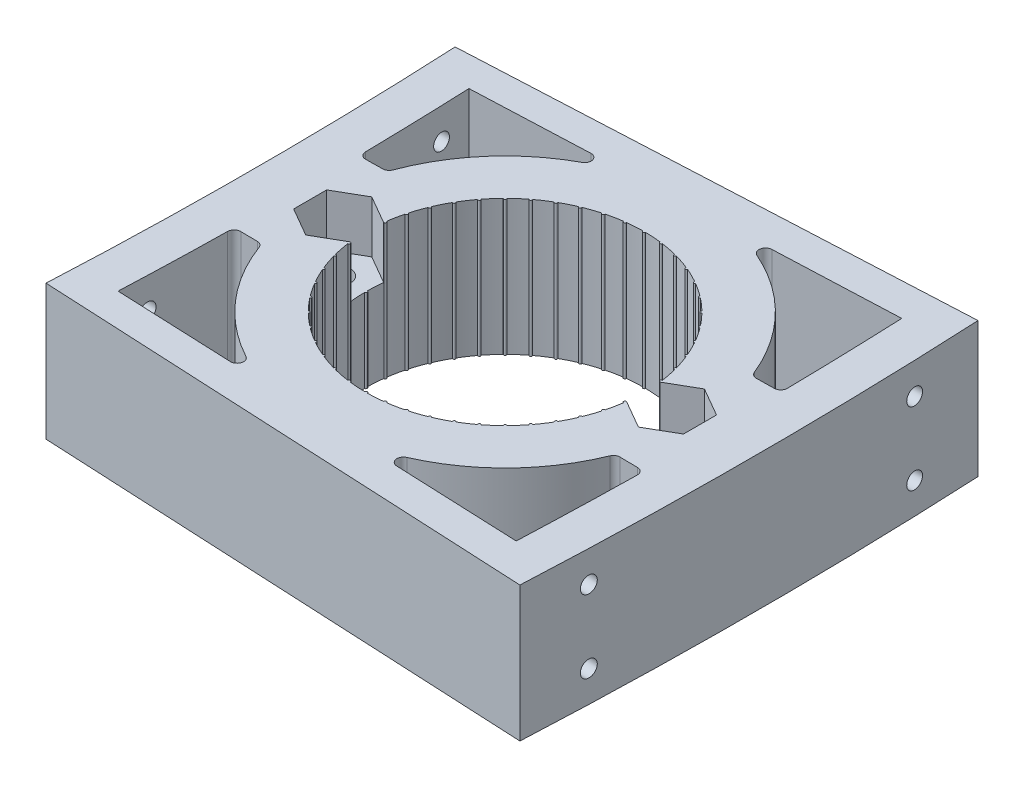
SolidWorks part; units mm, degrees
ref_plane "Front Plane" through (0, 0, 0) normal (0, 0, 1) x (1, 0, 0)
ref_plane "Top Plane" through (0, 0, 0) normal (0, 1, 0) x (1, 0, 0)
ref_plane "Right Plane" through (0, 0, 0) normal (1, 0, 0) x (0, 0, -1)
sketch "Sketch1" plane through (0, 0, 0) normal (0, 1, 0) x (1, 0, 0)
  line L0 (711.9611, 34.9764) -> (0, 0) construction
  line L1 (0, 0) -> (711.9611, -34.9764) construction
  line L2 (635.8529, 31.2375) -> (711.9611, 34.9764)
  line L3 (635.8529, -31.2375) -> (711.9611, -34.9764)
  circle A0 centre (0, 0) radius 636.6198 construction
  circle A1 centre (0, 0) radius 712.8198 construction
  arc A2 (711.9611, -34.9764) -> (711.9611, 34.9764) centre (0, 0) ccw
  arc A3 (635.8529, -31.2375) -> (635.8529, 31.2375) centre (0, 0) ccw
  dimension "D1" = 1273.2395
  dimension "D2" = 76.2
  dimension "D3" = 5.625
extrude "TrackTop" add sketch "Sketch1" along normal blind 20.6375
sketch "Sketch6" plane through (0, 0, 0) normal (0, 1, 0) x (1, 0, 0)
  line L0 (636.6198, 0) -> (0, 0) construction
  line L1 (636.6198, 0) -> (649.3198, 0) construction
  line L2 (649.3198, 0) -> (700.1198, 0) construction
  line L3 (700.1198, 0) -> (712.8198, 0) construction
  circle A0 centre (649.3198, 0) radius 1.8288
  circle A1 centre (700.1198, 0) radius 1.8288
  circle A4 centre (0, 0) radius 712.8198 construction
  circle A5 centre (0, 0) radius 636.6198 construction
  dimension "D1" = 3.6576
  dimension "D2" = 12.7
extrude "MountingHoles" cut sketch "Sketch6" along normal through all both and the other way through all
sketch "Sketch9" plane through (0, 0, 0) normal (0, 1, 0) x (1, 0, 0)
  line L0 (0, 0) -> (755.0104, 26.3655) construction
  line L1 (0, 0) -> (983.0347, 0) construction
  dimension "D1" = 2
sketch "Sketch7" plane through (0, 20.6375, 0) normal (0, 1, 0) x (1, 0, 0)
  line L0 (712.8198, 0) -> (636.6198, 0) construction
  arc A0 (711.9611, -34.9764) -> (711.9611, 34.9764) centre (0, 0) ccw construction
  arc A1 (635.8529, -31.2375) -> (635.8529, 31.2375) centre (0, 0) ccw construction
  circle A2 centre (674.7198, 0) radius 21.25
  dimension "D1" = 42.5
extrude "Cut-Extrude1" cut sketch "Sketch7" against normal through all
sketch "Sketch15" plane through (0, 0, 0) normal (0, 1, 0) x (1, 0, 0)
  line L0 (674.7198, 21.25) -> (674.7198, -21.25) construction
  circle A0 centre (674.7198, 0) radius 21.25 construction
  circle A1 centre (674.7198, 0) radius 21.25 construction
  circle A2 centre (674.7198, 21.25) radius 0.2
  point P2 (674.7198, 0)
  dimension "D1" = 0.4
sketch "Sketch16" plane through (0, 0, 0) normal (0, 0, 1) x (1, 0, 0)
  line L0 (674.7198, 0) -> (674.7198, 28.4843) construction
extrude "Boss-Extrude1" add sketch "Sketch15" along normal up to surface (20.6375 mm away) up to face at (674.7198, 20.6375, 21.25)
pattern_circular "CirPattern1" count 48 over 360 about axis through (674.7198, 0, 0) along (0, 1, 0) of "Boss-Extrude1" reverse direction yes
sketch "Sketch8" plane through (0, 20.6375, 0) normal (0, 1, 0) x (1, 0, 0)
  line L1 (653.6854, -2.5205) -> (653.6854, 2.5205)
  line L2 (653.6854, 2.5205) -> (649.3198, 5.041)
  line L3 (649.3198, 5.041) -> (644.9541, 2.5205)
  line L4 (644.9541, 2.5205) -> (644.9541, -2.5205)
  line L5 (644.9541, -2.5205) -> (649.3198, -5.041)
  line L6 (649.3198, -5.041) -> (653.6854, -2.5205)
  line L7 (704.4854, -2.5205) -> (704.4854, 2.5205)
  line L8 (704.4854, 2.5205) -> (700.1198, 5.041)
  line L9 (700.1198, 5.041) -> (695.7541, 2.5205)
  line L10 (695.7541, 2.5205) -> (695.7541, -2.5205)
  line L11 (695.7541, -2.5205) -> (700.1198, -5.041)
  line L12 (700.1198, -5.041) -> (704.4854, -2.5205)
  circle A0 centre (649.3198, 0) radius 4.3656 construction
  circle A1 centre (700.1198, 0) radius 4.3656 construction
  point P10 (644.9541, 0)
  dimension "D1" = 8.7312
extrude "Cut-Extrude2" cut sketch "Sketch8" against normal blind 7.9375
sketch "Sketch13" plane through (0, 20.6375, 0) normal (0, 1, 0) x (1, 0, 0)
  line L0 (642.4114, 26.7914) -> (705.8562, 29.4373) construction
  line L1 (642.4114, -26.7914) -> (705.8562, -29.4373) construction
  line L2 (642.4114, -26.7914) -> (0, 0) construction
  line L3 (642.4114, 26.7914) -> (0, 0) construction
  line L4 (-200000, 0) -> (200983.0347, 0) construction
  line L5 (635.8529, 31.2375) -> (711.9611, 34.9764) construction
  line L6 (642.8992, 9.525) -> (642.8992, -9.525) construction
  line L7 (706.3922, 10.4657) -> (701.9914, 10.4005)
  line L8 (642.8992, 9.525) -> (647.152, 9.588)
  line L9 (647.152, -9.588) -> (642.8992, -9.525)
  line L10 (706.3922, -10.4657) -> (701.9914, -10.4005)
  line L11 (642.8992, 9.525) -> (0, 0)
  line L12 (642.8992, -9.525) -> (0, 0)
  line L13 (665.7134, 27.7632) -> (642.4114, 26.7914)
  line L14 (705.8562, 29.4373) -> (681.3832, 28.4167)
  line L15 (705.8562, -29.4373) -> (681.3832, -28.4167)
  line L16 (665.7134, -27.7632) -> (642.4114, -26.7914)
  arc A0 (642.4114, -26.7914) -> (642.8992, -9.525) centre (0, 0) ccw
  arc A1 (705.8562, -29.4373) -> (706.3922, -10.4657) centre (0, 0) ccw
  arc A2 (642.8992, 9.525) -> (642.4114, 26.7914) centre (0, 0) ccw
  arc A3 (706.3922, 10.4657) -> (705.8562, 29.4373) centre (0, 0) ccw
  circle A4 centre (674.7198, 0) radius 29.1875 construction
  circle A5 centre (674.7198, 0) radius 21.25 construction
  arc A6 (635.8529, -31.2375) -> (635.8529, 31.2375) centre (0, 0) ccw construction
  arc A7 (711.9611, -34.9764) -> (711.9611, 34.9764) centre (0, 0) ccw construction
  arc A8 (647.152, 9.588) -> (665.7134, 27.7632) centre (674.7198, 0) cw
  arc A9 (701.9914, 10.4005) -> (681.3832, 28.4167) centre (674.7198, 0) ccw
  arc A10 (701.9914, -10.4005) -> (681.3832, -28.4167) centre (674.7198, 0) cw
  arc A11 (647.152, -9.588) -> (665.7134, -27.7632) centre (674.7198, 0) ccw
  point P18 (642.8992, 0)
  dimension "D2" = 6.35
  dimension "D3" = 6.35
  dimension "D5" = 7.9375
  dimension "D1" = 4.7625
  dimension "D4" = 19.05
extrude "Cut-Extrude5" cut sketch "Sketch13" against normal through all contours A11 L9 A0 L16 | L8 A8 L13 A2 | A9 L7 A3 L14 | L10 A10 L15 A1 region at (699.2431, 20.6375, -22.2451) region at (649.1861, 20.6375, -20.715) region at (649.1861, 20.6375, 20.715) region at (699.2431, 20.6375, 22.2451)
fillet "Fillet1" radius 1 12 edges at (647.152, 10.3187, 9.588) (642.8992, 10.3187, 9.525) (701.9914, 10.3187, 10.4005) (706.3922, 10.3187, 10.4657) (701.9914, 10.3187, -10.4005) (706.3922, 10.3187, -10.4657) (647.152, 10.3187, -9.588) (642.8992, 10.3187, -9.525) (665.7134, 10.3187, 27.7632) (681.3832, 10.3187, 28.4167) (665.7134, 10.3187, -27.7632) (681.3832, 10.3187, -28.4167)
ref_plane "Plane1" through (636.232, 0, -22.2177) normal (-0.9994, 0, 0.0349) x (0.0349, 0, 0.9994)
sketch "Sketch10" plane through (636.232, 0, -22.2177) normal (-0.9994, 0, 0.0349) x (0.0349, 0, 0.9994)
  line L0 (0, 0) -> (0, 20.6375) construction
  line L1 (59.8022, 20.6375) -> (-10.108, 20.6375) construction
  line L2 (0, 15.875) -> (0, 4.7625) construction
  circle A0 centre (0, 15.875) radius 1.25
  circle A1 centre (0, 4.7625) radius 1.25
  point P9 (0, 10.3187)
  dimension "D1" = 2.5
  dimension "D2" = 4.7625
extrude "Cut-Extrude3" cut sketch "Sketch10" against normal up to next and the other way through all
ref_plane "Plane2" through (712.3855, 0, -24.8771) normal (0.9994, 0, -0.0349) x (-0.0349, 0, -0.9994)
sketch "Sketch14" plane through (712.3855, 0, -24.8771) normal (0.9994, 0, -0.0349) x (-0.0349, 0, -0.9994)
  circle A0 centre (0, 15.875) radius 1.25 construction
  circle A1 centre (0, 15.875) radius 1.25
  circle A2 centre (0, 4.7625) radius 1.25 construction
  circle A3 centre (0, 4.7625) radius 1.25
extrude "Cut-Extrude6" cut sketch "Sketch14" against normal up to next and the other way through all
mirror "Mirror1" about plane through (0, 0, 0) normal (0, 0, 1) of "Cut-Extrude6", "Cut-Extrude3"
equation "\"InternalCircumference\"= 4m"
equation "\"D1@Sketch1\"=\"InternalCircumference\"/PI"
equation "\"TrackWidth\"=76.2"
equation "\"D2@Sketch1\"=\"TrackWidth\""
equation "\"WallStudDiameter\"=6.35"
equation "\"SandwichBoltDiameter\"= 0.1440in'6-32"
equation "\"HoleEdgeSpacing\"= 1in / 2"
equation "\"D2@Sketch6\"=\"HoleEdgeSpacing\""
equation "\"TeeNutWidth\"= 6.35'4-40"
equation "\"TeeNutHeight\"= 2.38125'4-40"
equation "\"TeeNutDrillSize\"= 3.048'4-40"
equation "\"HollowWallThickness\"=9.525"
equation "\"LegHoleDiameter\"= 42.5mm'1.25 in PVC"
equation "\"D3@Sketch1\"=360/64"
equation "\"D1@Sketch7\"=\"LegHoleDiameter\""
equation "\"D1@Sketch8\"=(5in/16)*1.1"
equation "\"4_40_Tap\"=2.5"
equation "\"D1@Sketch10\"=\"4_40_Tap\""
